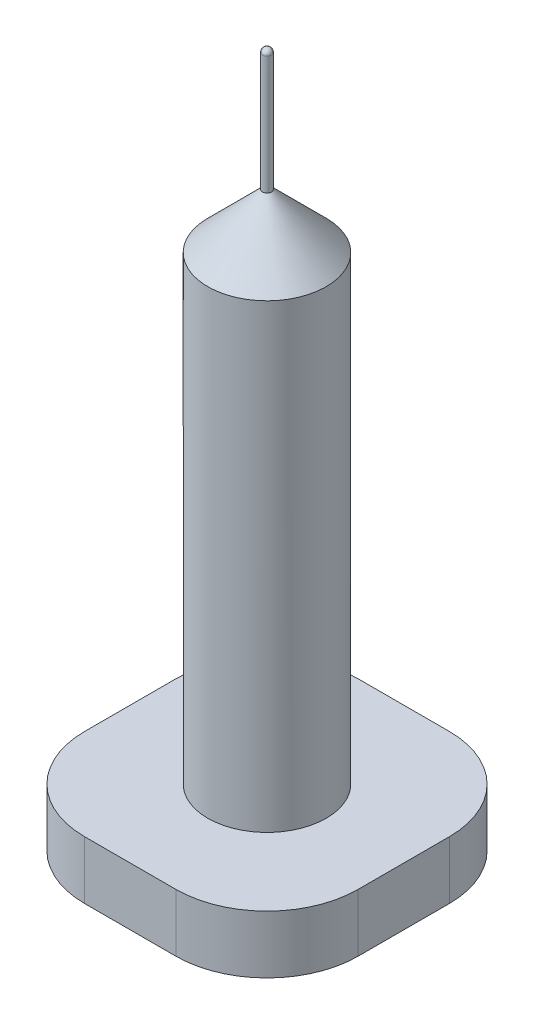
SolidWorks part; units mm, degrees
ref_plane "Front Plane" through (0, 0, 0) normal (0, 0, 1) x (1, 0, 0)
ref_plane "Top Plane" through (0, 0, 0) normal (0, 1, 0) x (1, 0, 0)
ref_plane "Right Plane" through (0, 0, 0) normal (1, 0, 0) x (0, 0, -1)
sketch "Sketch2" plane through (0, 0, 0) normal (0, 1, 0) x (1, 0, 0)
  line L1 (-15, -15) -> (15, -15)
  line L2 (-15, -15) -> (-15, 15)
  line L3 (-15, 15) -> (15, 15)
  line L4 (15, -15) -> (15, 15)
  line L5 (-15, -15) -> (15, 15) construction
  line L6 (-15, 15) -> (15, -15) construction
  point P0 (0, 0)
  dimension "D1" = 30
  dimension "D2" = 30
extrude "Boss-Extrude1" add sketch "Sketch2" along normal blind 6.35 contours L1 L4 L3 L2 region at (0, 0, 0)
fillet "Fillet1" radius 10 4 edges at (-15, 3.175, -15) (-15, 3.175, 15) (15, 3.175, -15) (15, 3.175, 15)
sketch "Sketch3" plane through (0, 6.35, 0) normal (0, 1, 0) x (1, 0, 0)
  circle A0 centre (0, 0) radius 6.5
  dimension "D1" = 13
extrude "Boss-Extrude2" add sketch "Sketch3" along normal blind 50
sketch "Sketch4" plane through (0, 56.35, 0) normal (0, 1, 0) x (1, 0, 0)
  circle A0 centre (0, 0) radius 0.5
  dimension "D1" = 1
extrude "Boss-Extrude3" add sketch "Sketch4" along normal blind 20
fillet "Fillet2" radius 0.5 1 edges at (0, 76.35, 0.5)
chamfer "Chamfer1" distance 6.5 angle 45 1 edges at (0, 56.35, 0.5)
